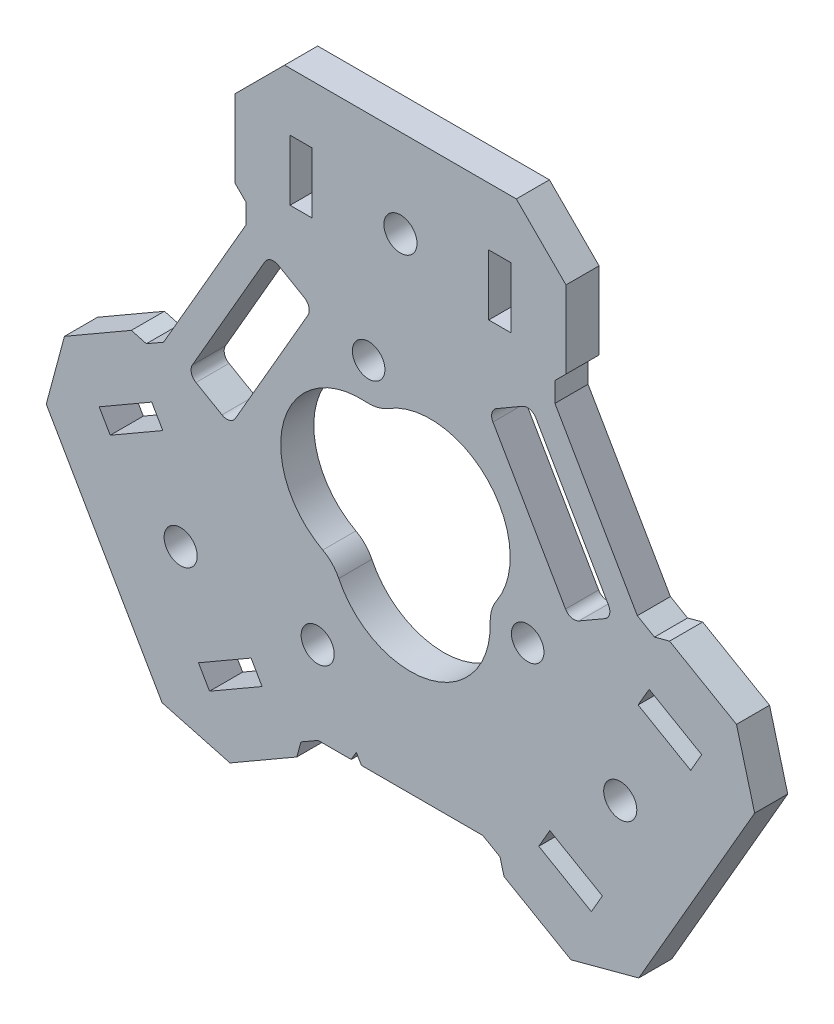
SolidWorks part; units mm, degrees
material "Teak"
ref_plane "Front Plane" through (0, 0, 0) normal (0, 0, 1) x (1, 0, 0)
ref_plane "Top Plane" through (0, 0, 0) normal (0, 1, 0) x (1, 0, 0)
ref_plane "Right Plane" through (0, 0, 0) normal (1, 0, 0) x (0, 0, -1)
sketch "Sketch1" plane through (0, 0, 0) normal (0, 0, 1) x (1, 0, 0)
  line L0 (8, 23) -> (8, 25.75)
  line L1 (0, -20.4762) -> (7.4659, -20.4762)
  line L2 (9.0215, -21.3744) -> (7.4659, -20.4762)
  line L3 (9.3875, -22.7404) -> (9.0215, -21.3744)
  line L4 (11.1369, -23.7504) -> (9.3875, -22.7404)
  line L5 (13.6369, -19.4203) -> (11.1369, -23.7504) construction
  line L6 (12.537, -18.7853) -> (13.6369, -19.4203)
  line L7 (8, 25.75) -> (10, 25.75)
  line L8 (10, 25.75) -> (10, 23)
  line L9 (13.537, -17.0532) -> (12.537, -18.7853)
  line L10 (0, 0) -> (0, 23) construction
  line L11 (-15, 23) -> (15, 23) construction
  line L12 (-8, 23) -> (-8, 20.25)
  line L13 (-8, 20.25) -> (-10, 20.25)
  line L14 (10, 20.25) -> (10, 23)
  line L15 (8, 20.25) -> (10, 20.25)
  line L16 (-10, 20.25) -> (-10, 23)
  line L17 (-10, 21.52) -> (-15, 21.52) construction
  line L18 (-15, 23) -> (-15, 19.5)
  line L19 (-15, 19.5) -> (-14, 18.5)
  line L20 (-14, 18.5) -> (-14, 16.7038)
  line L21 (8, 23) -> (8, 20.25)
  line L22 (15.9186, -18.4282) -> (13.537, -17.0532)
  line L23 (-15, 23) -> (-15, 26.5)
  line L24 (15.9186, -18.4282) -> (18.3002, -19.8032)
  line L25 (-10, 24.48) -> (-15, 24.48) construction
  line L26 (-10, 25.75) -> (-10, 23)
  line L27 (18.3002, -19.8032) -> (17.3002, -21.5353)
  line L28 (17.3002, -21.5353) -> (13.6369, -19.4203)
  line L29 (-8, 25.75) -> (-10, 25.75)
  line L30 (-8, 23) -> (-8, 25.75)
  line L31 (0, 23) -> (0, 31) construction
  line L32 (-15, 26.5) -> (-10.5, 31)
  line L33 (-10.5, 31) -> (10.5, 31)
  line L34 (14, 18.5) -> (14, 16.7038)
  line L35 (15, 19.5) -> (14, 18.5)
  line L36 (15, 23) -> (15, 19.5)
  line L37 (10, 21.52) -> (15, 21.52) construction
  line L38 (16.2003, -20.9003) -> (13.7003, -25.2304) construction
  line L39 (11.1369, -23.7504) -> (15.4497, -26.2404)
  line L40 (15.4497, -26.2404) -> (21.5968, -24.5933)
  line L41 (32.0968, -6.4067) -> (21.5968, -24.5933)
  line L42 (30.4497, -0.2596) -> (32.0968, -6.4067)
  line L43 (26.1369, 2.2304) -> (30.4497, -0.2596)
  line L44 (26.2003, -3.5797) -> (28.7003, 0.7504) construction
  line L45 (27.3002, -4.2147) -> (23.6369, -2.0997)
  line L46 (26.3002, -5.9468) -> (27.3002, -4.2147)
  line L47 (23.9186, -4.5718) -> (26.3002, -5.9468)
  line L48 (23.9186, -4.5718) -> (21.537, -3.1968)
  line L49 (21.537, -3.1968) -> (22.537, -1.4647)
  line L50 (22.537, -1.4647) -> (23.6369, -2.0997)
  line L51 (10, 24.48) -> (15, 24.48) construction
  line L52 (15, 23) -> (15, 26.5)
  line L53 (15, 26.5) -> (10.5, 31)
  line L54 (23.6369, -2.0997) -> (26.1369, 2.2304) construction
  line L55 (26.1369, 2.2304) -> (24.3875, 3.2404)
  line L56 (24.3875, 3.2404) -> (23.0215, 2.8744)
  line L57 (23.0215, 2.8744) -> (21.4659, 3.7725)
  line L58 (21.4659, 3.7725) -> (17.7329, 10.2381)
  line L59 (-17.7329, 10.2381) -> (-21.4659, 3.7725)
  line L60 (-23.0215, 2.8744) -> (-21.4659, 3.7725)
  line L61 (-24.3875, 3.2404) -> (-23.0215, 2.8744)
  line L62 (-26.1369, 2.2304) -> (-24.3875, 3.2404)
  line L63 (-23.6369, -2.0997) -> (-26.1369, 2.2304) construction
  line L64 (-22.537, -1.4647) -> (-23.6369, -2.0997)
  line L65 (-21.537, -3.1968) -> (-22.537, -1.4647)
  line L66 (-23.9186, -4.5718) -> (-21.537, -3.1968)
  line L67 (-23.9186, -4.5718) -> (-26.3002, -5.9468)
  line L68 (-26.3002, -5.9468) -> (-27.3002, -4.2147)
  line L69 (-27.3002, -4.2147) -> (-23.6369, -2.0997)
  line L70 (-26.2003, -3.5797) -> (-28.7003, 0.7504) construction
  line L71 (-26.1369, 2.2304) -> (-30.4497, -0.2596)
  line L72 (-30.4497, -0.2596) -> (-32.0968, -6.4067)
  line L73 (-21.5968, -24.5933) -> (-32.0968, -6.4067)
  line L74 (-15.4497, -26.2404) -> (-21.5968, -24.5933)
  line L75 (-11.1369, -23.7504) -> (-15.4497, -26.2404)
  line L76 (-16.2003, -20.9003) -> (-13.7003, -25.2304) construction
  line L77 (-17.3002, -21.5353) -> (-13.6369, -19.4203)
  line L78 (-18.3002, -19.8032) -> (-17.3002, -21.5353)
  line L79 (-15.9186, -18.4282) -> (-18.3002, -19.8032)
  line L80 (-15.9186, -18.4282) -> (-13.537, -17.0532)
  line L81 (-13.537, -17.0532) -> (-12.537, -18.7853)
  line L82 (-12.537, -18.7853) -> (-13.6369, -19.4203)
  line L83 (-13.6369, -19.4203) -> (-11.1369, -23.7504) construction
  line L84 (-11.1369, -23.7504) -> (-9.3875, -22.7404)
  line L85 (-9.3875, -22.7404) -> (-9.0215, -21.3744)
  line L86 (-9.0215, -21.3744) -> (-7.4659, -20.4762)
  line L87 (-7.4659, -20.4762) -> (0, -20.4762)
  line L136 (-14, 16.7038) -> (-17.7329, 10.2381)
  line L138 (17.7329, 10.2381) -> (14, 16.7038)
  line L139 (0, 0) -> (0, -20.4762) construction
  line L140 (0, 0) -> (17.7329, 10.2381) construction
  line L141 (0, 0) -> (-17.7329, 10.2381) construction
  circle A0 centre (0, 23) radius 1.5
  circle A1 centre (19.9186, -11.5) radius 1.5
  circle A2 centre (0, 0) radius 1.6 construction
  circle A3 centre (-19.9186, -11.5) radius 1.5
  point P0 (0, 0)
  point P32 (-8, 23)
  point P102 (0, 0)
  point P108 (0, 0)
  point P148 (0, 0)
  dimension "D4" = 3
  dimension "D5" = 3
  dimension "D2" = 120
  dimension "D3" = 2
  dimension "D6" = 5
  dimension "D7" = 1.48
  dimension "D8" = 3
  dimension "D9" = 5.5
  dimension "D10" = 20.4762
  dimension "D11" = 30
  dimension "D14" = 23
  dimension "D15" = 7
  dimension "D16" = 45
  dimension "D17" = 8
  dimension "D18" = 1
extrude "Boss-Extrude1" add sketch "Sketch1" along normal blind 3
ref_axis "Axis1" through (0, 0, -0.15) along (0, 0, 1)
sketch "Sketch3" plane through (0, 0, 3) normal (0, 0, 1) x (1, 0, 0)
  line L1 (-14, 14) -> (14, 14) construction
  line L2 (-14, 14) -> (-14, -14) construction
  line L3 (-14, -14) -> (14, -14) construction
  line L4 (14, 14) -> (14, -14) construction
  line L5 (-14, 14) -> (14, -14) construction
  line L6 (-14, -14) -> (14, 14) construction
  circle A0 centre (0, 0) radius 8.6
  circle A1 centre (-14, -14) radius 1.6 construction
  circle A2 centre (-14, 14) radius 1.6 construction
  circle A3 centre (14, 14) radius 1.6 construction
  circle A4 centre (14, -14) radius 1.6 construction
  dimension "D1" = 3.2
  dimension "D3" = 17.2
  dimension "D2" = 28
extrude "Cut-Extrude2" cut sketch "Sketch3" against normal through all
sketch "Sketch4" plane through (0, 0, 3) normal (0, 0, 1) x (1, 0, 0)
  line L0 (0, 0) -> (0.7383, 0.7383) construction
  line L1 (7.5, 12.9904) -> (-7.5, 12.9904) construction
  line L2 (-7.5, 12.9904) -> (-15, 0) construction
  line L3 (-15, 0) -> (-7.5, -12.9904) construction
  line L4 (-7.5, -12.9904) -> (7.5, -12.9904) construction
  line L5 (7.5, -12.9904) -> (15, 0) construction
  line L6 (15, 0) -> (7.5, 12.9904) construction
  line L7 (12.3365, -0.3156) -> (9.325, -1.1226) construction
  line L8 (9.325, -1.1226) -> (8.5181, -4.134) construction
  line L9 (8.5181, -4.134) -> (10.7226, -6.3386) construction
  line L10 (10.7226, -6.3386) -> (13.7341, -5.5316) construction
  line L11 (13.7341, -5.5316) -> (14.541, -2.5202) construction
  line L12 (14.541, -2.5202) -> (12.3365, -0.3156) construction
  line L13 (0.3691, 0.3691) -> (6.0104, 6.0104) construction
  line L14 (6.0104, 6.0104) -> (16.8169, -4.7961) construction
  line L15 (-7.4659, -20.4762) -> (7.4659, -20.4762) construction
  circle A0 centre (0, 0) radius 12.9904 construction
  circle A1 centre (-7.5, 12.9904) radius 1.5 construction
  circle A2 centre (7.5, 12.9904) radius 1.5 construction
  circle A3 centre (15, 0) radius 1.5 construction
  circle A4 centre (7.5, -12.9904) radius 1.5 construction
  circle A5 centre (-7.5, -12.9904) radius 1.5
  circle A6 centre (-15, 0) radius 1.5 construction
  circle A7 centre (-8.6461, -8.3213) radius 1.475 construction
  circle A8 centre (-8.6461, -8.3213) radius 3.5 construction
  circle A9 centre (0, 0) radius 8.5 construction
  circle A10 centre (-2.8834, 11.6484) radius 1.475
  circle A11 centre (11.5295, -3.3271) radius 1.475
  circle A12 centre (11.5295, -3.3271) radius 2.7 construction
  point P22 (0, 0)
  point P31 (0, 0)
  point P32 (0, 0)
  dimension "D2" = 3
  dimension "D4" = 17
  dimension "D5" = 7
  dimension "D6" = 2.95
  dimension "D9" = 5.4
  dimension "D1" = 15
  dimension "D8" = 45
  dimension "D3" = 6
  dimension "D7" = 3
extrude "Cut-Extrude3" cut sketch "Sketch4" against normal through all
sketch "Sketch5" plane through (0, 0, 3) normal (0, 0, 1) x (1, 0, 0)
  line L0 (-14.4119, 4.1589) -> (0, 0) construction
  line L1 (0, 0) -> (10.8077, 10.4017) construction
  line L2 (0, 0) -> (3.6043, -14.5605) construction
  line L3 (0, 0) -> (-8.6461, -8.3213) construction
  line L4 (0, 0) -> (-2.8834, 11.6484) construction
  circle A0 centre (-14.4119, 4.1589) radius 4 construction
  circle A1 centre (10.8077, 10.4017) radius 4 construction
  circle A2 centre (-7.5, -12.9904) radius 4 construction
  arc A3 (-5.5904, -6.8305) -> (-7.0395, -5.3249) centre (-8.6461, -8.3213) ccw
  arc A4 (-3.1202, 8.2567) -> (-1.0918, 8.7588) centre (-2.8834, 11.6484) ccw
  arc A5 (8.7106, -1.4262) -> (8.1312, -3.4339) centre (11.5295, -3.3271) ccw
  circle A6 centre (0, 0) radius 8.6 construction
  arc A7 (-7.0395, -5.3249) -> (-3.1202, 8.2567) centre (-3.6236, 1.0457) cw
  arc A8 (-1.0918, 8.7588) -> (8.7106, -1.4262) centre (2.7174, 2.6153) cw
  arc A9 (8.1312, -3.4339) -> (-5.5904, -6.8305) centre (0.9062, -3.6609) cw
  circle A10 centre (0, 0) radius 15 construction
  circle A11 centre (-7.5, -12.9904) radius 1.5 construction
  circle A12 centre (3.6043, -14.5605) radius 4 construction
  dimension "D1" = 8
  dimension "D2" = 120
  dimension "D3" = 120
  dimension "D4" = 120
extrude "Cut-Extrude4" cut sketch "Sketch5" against normal through all
sketch "Sketch6" plane through (0, 0, 3) normal (0, 0, 1) x (1, 0, 0)
  line L0 (0, 0) -> (23.3827, -13.5) construction
  line L3 (31.1992, -6.4659) -> (31.8468, -6.8397)
  line L4 (21.5968, -24.5933) -> (32.0968, -6.4067) construction
  line L5 (21.1992, -23.7864) -> (21.8468, -24.1603)
  line L6 (21.8468, -24.1603) -> (31.8468, -6.8397)
  arc A0 (31.1992, -6.4659) -> (21.1992, -23.7864) centre (38.1051, -22) ccw
  point P3 (19.9186, -11.5)
  point P4 (26.8468, -15.5)
  dimension "D1" = 4
  dimension "D2" = 20
  dimension "D3" = 17
extrude "Cut-Extrude5" [suppressed] cut sketch "Sketch6" against normal through all
pattern_circular "CirPattern1" [suppressed] count 3 over 360 about axis through (0, 0, -0.15) along (0, 0, 1) of bodies 110
sketch "Sketch7" plane through (0, 0, 3) normal (0, 0, 1) x (1, 0, 0)
  line L0 (12.2799, 14.683) -> (18.8558, 3.2932)
  line L1 (-12.2799, 14.683) -> (-18.8558, 3.2932)
  line L2 (-11.0642, 15.0088) -> (-8.7086, 13.6488)
  line L3 (-18.5301, 2.0775) -> (-16.1745, 0.7175)
  line L4 (-8.3828, 12.433) -> (-14.9587, 1.0432)
  line L5 (11.0642, 15.0088) -> (8.7086, 13.6488)
  line L6 (18.5301, 2.0775) -> (16.1745, 0.7175)
  line L7 (8.3828, 12.433) -> (14.9587, 1.0432)
  line L9 (21.4659, 3.7725) -> (14, 16.7038) construction
  line L10 (-14, 16.7038) -> (-21.4659, 3.7725) construction
  arc A0 (14.9587, 1.0432) -> (16.1745, 0.7175) centre (15.7295, 1.4882) ccw
  arc A1 (18.5301, 2.0775) -> (18.8558, 3.2932) centre (18.0851, 2.8482) ccw
  arc A2 (12.2799, 14.683) -> (11.0642, 15.0088) centre (11.5092, 14.238) ccw
  arc A3 (8.7086, 13.6488) -> (8.3828, 12.433) centre (9.1536, 12.878) ccw
  arc A4 (-16.1745, 0.7175) -> (-14.9587, 1.0432) centre (-15.7295, 1.4882) ccw
  arc A5 (-8.3828, 12.433) -> (-8.7086, 13.6488) centre (-9.1536, 12.878) ccw
  arc A6 (-11.0642, 15.0088) -> (-12.2799, 14.683) centre (-11.5092, 14.238) ccw
  arc A7 (-18.8558, 3.2932) -> (-18.5301, 2.0775) centre (-18.0851, 2.8482) ccw
  dimension "D1" = 0.89
  dimension "D2" = 2.5
  dimension "D3" = 4.5
  dimension "D4" = 2.5
  dimension "D5" = 4.5
extrude "Cut-Extrude6" cut sketch "Sketch7" against normal through all
sketch "Sketch8" plane through (0, 0, 3) normal (0, 0, 1) x (1, 0, 0)
  line L0 (-3.5381, -20.4762) -> (-4, -19.6762)
  line L1 (-7.4659, -20.4762) -> (7.4659, -20.4762) construction
  line L2 (-4, -19.6762) -> (-4.4619, -20.4762)
  line L3 (-4.4619, -20.4762) -> (-3.5381, -20.4762)
  dimension "D1" = 0.8
  dimension "D2" = 4
extrude "Cut-Extrude7" cut sketch "Sketch8" against normal through all
